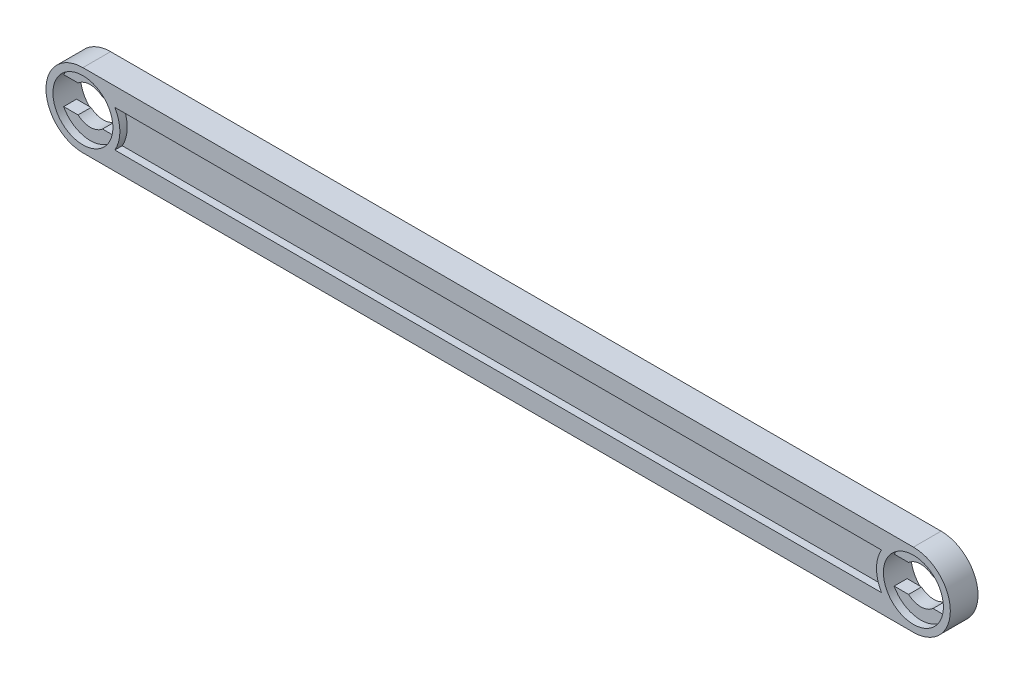
SolidWorks part; units mm, degrees
ref_plane "前视基准面" through (0, 0, 0) normal (0, 0, 1) x (1, 0, 0)
ref_plane "上视基准面" through (0, 0, 0) normal (0, 1, 0) x (1, 0, 0)
ref_plane "右视基准面" through (0, 0, 0) normal (1, 0, 0) x (0, 0, -1)
sketch "草图1" plane through (0, 0, 0) normal (0, 0, 1) x (1, 0, 0)
  line L1 (0, 4) -> (90, 4)
  line L3 (0, -4) -> (90, -4)
  arc A0 (0, 4) -> (0, -4) centre (0, 0) ccw
  arc A2 (90, -4) -> (90, 4) centre (90, 0) ccw
extrude "凸台-拉伸1" add sketch "草图1" against normal blind 3
sketch "草图2" plane through (0, 0, 0) normal (0, 0, 1) x (1, 0, 0)
  line L0 (1.3229, -1.5) -> (2.8831, -1.5)
  line L1 (-2.8831, -1.5) -> (-1.3229, -1.5)
  line L2 (1.3229, 1.5) -> (2.8831, 1.5)
  line L3 (-2.8831, 1.5) -> (-1.3229, 1.5)
  arc A0 (1.3229, 1.5) -> (-1.3229, 1.5) centre (0, 0) ccw
  arc A1 (-2.8831, 1.5) -> (-2.8831, -1.5) centre (0, 0) ccw
  arc A3 (2.8831, -1.5) -> (2.8831, 1.5) centre (0, 0) ccw
  arc A4 (-1.3229, -1.5) -> (1.3229, -1.5) centre (0, 0) ccw
extrude "切除-拉伸1" cut sketch "草图2" against normal up to next
sketch "草图3" plane through (0, 0, 0) normal (0, 0, 1) x (1, 0, 0)
  circle A1 centre (0, 0) radius 3.25
extrude "切除-拉伸2" cut sketch "草图3" against normal blind 0.8
extrude "切除-拉伸3" cut sketch "草图3<2>" along normal blind 0.8 from offset 3 offset against normal yes
sketch "草图3<2>" plane through (0, 0, 0) normal (0, 0, 1) x (1, 0, 0) same geometry as "草图3"
ref_plane "基准面1" through (45, 0, 0) normal (1, 0, 0) x (0, 0, -1)
mirror "镜向1" about plane through (45, 0, 0) normal (1, 0, 0) of "切除-拉伸3", "切除-拉伸2", "切除-拉伸1"
sketch "草图4" plane through (0, 0, 0) normal (0, 0, 1) x (1, 0, 0)
  line L0 (3.4641, 2) -> (86.5359, 2)
  line L2 (3.4641, -2) -> (86.5359, -2)
  arc A0 (3.4641, -2) -> (3.4641, 2) centre (0, 0) ccw
  arc A1 (86.5359, 2) -> (86.5359, -2) centre (90, 0) ccw
extrude "切除-拉伸4" cut sketch "草图4" against normal blind 0.8
sketch "草图5" plane through (0, 0, -3) normal (0, 0, -1) x (-1, 0, 0)
  line L1 (-86, -2) -> (-4, -2)
  line L2 (-86, -2) -> (-86, 2)
  line L3 (-86, 2) -> (-4, 2)
  line L4 (-4, -2) -> (-4, 2)
extrude "切除-拉伸5" cut sketch "草图5" against normal blind 0.8
